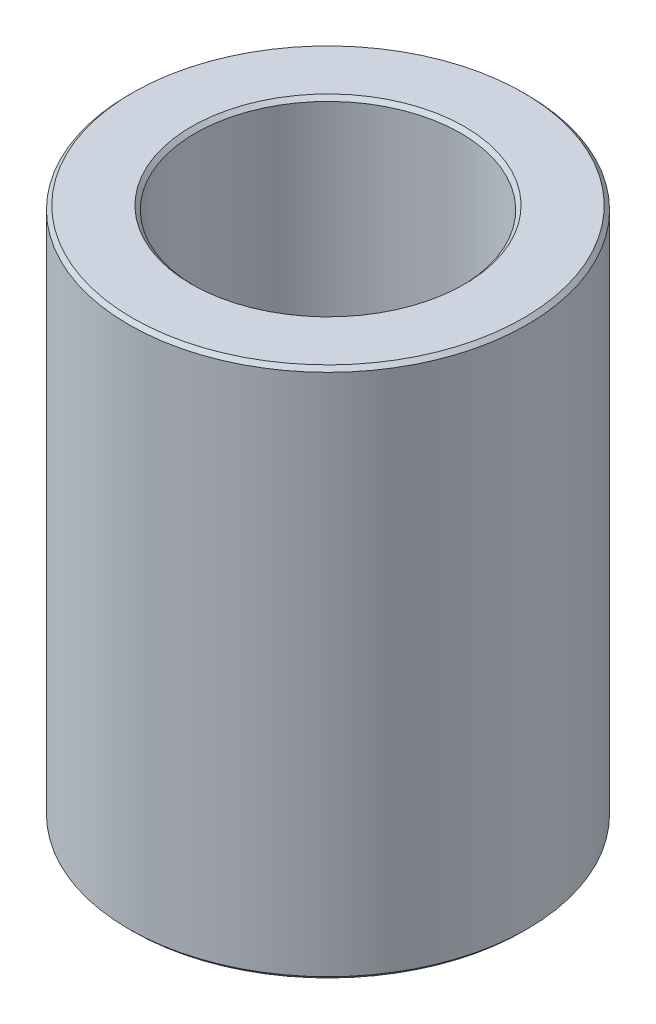
SolidWorks part; units mm, degrees
ref_plane "Ebene vorne" through (0, 0, 0) normal (0, 0, 1) x (1, 0, 0)
ref_plane "Ebene oben" through (0, 0, 0) normal (0, 1, 0) x (1, 0, 0)
ref_plane "Ebene rechts" through (0, 0, 0) normal (1, 0, 0) x (0, 0, -1)
sketch "Skizze1" plane through (0, 0, 0) normal (0, 1, 0) x (1, 0, 0)
  circle A0 centre (0, 0) radius 7
  circle A1 centre (0, 0) radius 10.5
  dimension "D1" = 21
  dimension "D2" = 14
extrude "Aufsatz-Linear austragen1" add sketch "Skizze1" along normal blind 14 and the other way blind 14
chamfer "Fase1" distance 0.2 angle 45 4 edges at (0, -14, 7) (0, -14, 10.5) (0, 14, 10.5) (0, 14, 7)
ref_axis "Achse1" through (0, 15.4, 0) along (0, -1, 0)
